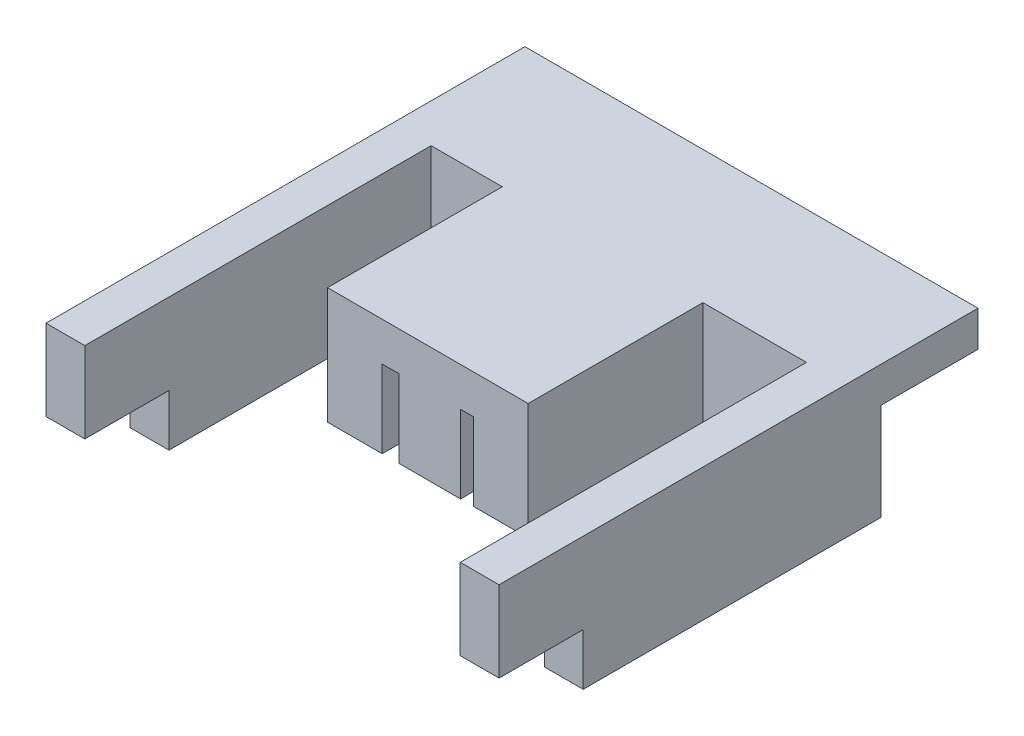
SolidWorks part; units mm, degrees
material "PBT General Purpose"
ref_plane "Front Plane" through (0, 0, 0) normal (0, 0, 1) x (1, 0, 0)
ref_plane "Top Plane" through (0, 0, 0) normal (0, 1, 0) x (1, 0, 0)
ref_plane "Right Plane" through (0, 0, 0) normal (1, 0, 0) x (0, 0, -1)
sketch "Sketch1" plane through (0, 0, 0) normal (0, 1, 0) x (1, 0, 0)
  line L0 (29, -29.5) -> (35, -29.5)
  line L1 (-35, 29.5) -> (35, 29.5)
  line L2 (-35, 29.5) -> (-35, -29.5)
  line L3 (-35, -29.5) -> (-29, -29.5)
  line L4 (35, 29.5) -> (35, -29.5)
  line L5 (-29, 24) -> (29, 24)
  line L6 (-29, 24) -> (-29, -29.5)
  line L8 (29, 24) -> (29, -29.5)
  point P8 (0, 24)
  point P10 (-35, 0)
  dimension "D1" = 70
  dimension "D2" = 59
  dimension "D3" = 6
  dimension "D4" = 5.5
  dimension "D5" = 6
extrude "Boss-Extrude1" add sketch "Sketch1" along normal blind 20.5
sketch "Sketch2" plane through (0, 0, 0) normal (0, -1, 0) x (1, 0, 0)
  line L0 (35, 29.5) -> (35, -29.5) construction
  line L1 (29, 29.5) -> (35, 29.5)
  line L2 (29, 29.5) -> (29, 16.5)
  line L3 (29, 16.5) -> (35, 16.5)
  line L4 (35, 29.5) -> (35, 16.5)
  line L5 (0, -1000) -> (0, 49000) construction
  line L6 (-29, -24) -> (29, -24) construction
  line L7 (-12.5, -24) -> (12.5, -24)
  line L8 (-12.5, -24) -> (-12.5, -29.5)
  line L9 (-12.5, -29.5) -> (12.5, -29.5)
  line L10 (12.5, -24) -> (12.5, -29.5)
  line L11 (35, -29.5) -> (-35, -29.5) construction
  line L12 (-29, 16.5) -> (-35, 16.5)
  line L13 (-35, 29.5) -> (-35, 16.5)
  line L14 (-29, 29.5) -> (-35, 29.5)
  line L15 (-29, 29.5) -> (-29, 16.5)
  point P18 (0, -24)
  point P19 (0, -24)
  dimension "D1" = 13
  dimension "D2" = 25
extrude "Cut-Extrude1" cut sketch "Sketch2" against normal blind 8
sketch "Sketch3" plane through (0, 20.5, 0) normal (0, 1, 0) x (1, 0, 0)
  line L0 (-29, -29.5) -> (-29, 24) construction
  line L1 (-14, 24) -> (9, 24)
  line L2 (-14, 24) -> (-14, 1)
  line L3 (-14, 1) -> (9, 1)
  line L4 (9, 24) -> (9, 1)
  line L6 (-29, 24) -> (29, 24) construction
  dimension "D1" = 23
  dimension "D2" = 23
  dimension "D3" = 15
extrude "Boss-Extrude2" add sketch "Sketch3" against normal offset from surface (6 mm away) 14.5 separate body up to face at (-25.5, 0, -12.3333)
sketch "Sketch4" plane through (0, 20.5, 0) normal (0, 1, 0) x (1, 0, 0)
  line L0 (-18, 24) -> (-18, -3)
  line L1 (-29, 24) -> (29, 24) construction
  line L2 (-18, -3) -> (13, -3)
  line L3 (13, -3) -> (13, 24)
  line L4 (-14, 24) -> (-14, 1)
  line L5 (-14, 1) -> (9, 1)
  line L6 (9, 1) -> (9, 24)
  line L7 (9, 24) -> (-14, 24)
  line L8 (-14, 24) -> (-14, 1)
  line L9 (-14, 1) -> (9, 1)
  line L10 (9, 1) -> (9, 24)
  line L11 (9, 24) -> (-14, 24)
  line L12 (13, 24) -> (-18, 24)
  line M12 (-29, 24) -> (29, 24)
  dimension "D2" = 4
  dimension "D3" = 4
  dimension "D4" = 4
  dimension "D1" = 0
extrude "Boss-Extrude4" add sketch "Sketch4" against normal offset from surface (18 mm away) 12 contours L2 L3 L0 L11 L10 L9 L8 M12 region at (-16, 20.5, -23.5889) up to face at (-2.5, 14.5, -12.5) offset beyond the face yes
sketch "Sketch5" plane through (0, 0, 0) normal (0, -1, 0) x (1, 0, 0)
  line L1 (-6.95, -24) -> (-9.55, -24)
  line L2 (-6.95, -24) -> (-6.95, -29.5)
  line L3 (-6.95, -29.5) -> (-9.55, -29.5)
  line L4 (-9.55, -24) -> (-9.55, -29.5)
  line L7 (-9.55, -1) -> (-6.95, -1)
  line L8 (-9.55, -1) -> (-9.55, 3)
  line L9 (-9.55, 3) -> (-6.95, 3)
  line L10 (-6.95, -1) -> (-6.95, 3)
  line L13 (-18, -1) -> (-14, -1)
  line L14 (-18, -1) -> (-18, -16)
  line L15 (-18, -16) -> (-14, -16)
  line L16 (-14, -1) -> (-14, -16)
  line L17 (-14, -1) -> (-14, -24) construction
  line L18 (9, -1) -> (-14, -1) construction
  line L19 (2.55, 3) -> (4.55, 3)
  line L20 (2.55, 3) -> (2.55, -1)
  line L21 (2.55, -1) -> (4.55, -1)
  line L22 (4.55, 3) -> (4.55, -1)
  line L24 (-12.5, -29.5) -> (12.5, -29.5) construction
  line L25 (9, -24) -> (-12.5, -24) construction
  line L26 (9, -1) -> (-14, -1) construction
  line L27 (13, 3) -> (-18, 3) construction
  line L28 (-18, 3) -> (-18, -24) construction
  point P14 (0, 0)
  point P15 (0, 0)
  point P32 (0, 0)
  point P33 (0, 0)
  point P34 (0, 0)
  point P37 (0, 0)
  dimension "D1" = 2
  dimension "D2" = 9.5
  dimension "D3" = 15
  dimension "D4" = 2.6
  dimension "D5" = 4.45
extrude "Cut-Extrude2" cut sketch "Sketch5" against normal up to surface (14.5 mm away) up to face at (-2.5, 14.5, -12.5)
sketch "Sketch9" plane through (0, 0, -29.5) normal (0, 0, -1) x (-1, 0, 0)
  line L0 (35, 20.5) -> (35, 0) construction
  line L1 (-35, 20.5) -> (35, 20.5)
  line L2 (-35, 20.5) -> (-35, 15)
  line L3 (-35, 15) -> (35, 15)
  line L4 (35, 20.5) -> (35, 15)
  dimension "D1" = 5.5
extrude "Boss-Extrude6" add sketch "Sketch9" along normal blind 15
sketch "Sketch10" plane through (0, 15, 0) normal (0, -1, 0) x (1, 0, 0)
  line L1 (35, -44.5) -> (-35, -44.5) construction
  line L3 (35, -29.5) -> (-35, -29.5) construction
  line L4 (11.5, -29.5) -> (-11.5, -29.5)
  line L6 (-14.5, -37) -> (14.5, -37)
  line L7 (-14.5, -37) -> (-11.5, -29.5)
  line L8 (14.5, -37) -> (11.5, -29.5)
  point P4 (20.7558, -37)
  point P5 (0, -44.5)
  point P6 (0, -37)
  dimension "D1" = 23
  dimension "D2" = 7.5
  dimension "D3" = 3
  dimension "D4" = 3
extrude "Boss-Extrude7" add sketch "Sketch10" along normal blind 7.5
equation "\"body_height\"= 41mm"
equation "\"D1@Boss-Extrude1\"=\"body_height\" / 2"
equation "\"D1@Boss-Extrude2\"=12+2.5"
